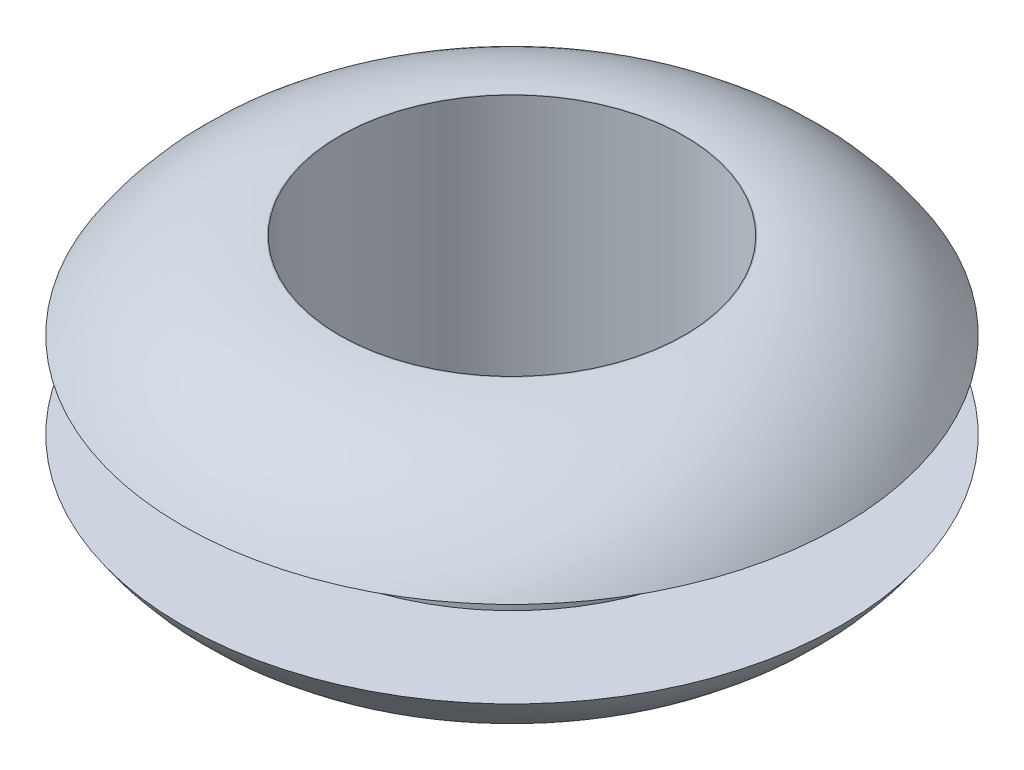
SolidWorks part; units mm, degrees
ref_plane "Front Plane" through (0, 0, 0) normal (0, 0, 1) x (1, 0, 0)
ref_plane "Top Plane" through (0, 0, 0) normal (0, 1, 0) x (1, 0, 0)
ref_plane "Right Plane" through (0, 0, 0) normal (1, 0, 0) x (0, 0, -1)
sketch "Sketch1" plane through (0, 0, 0) normal (0, 1, 0) x (1, 0, 0)
  circle A0 centre (0, 0) radius 7.65
  circle A1 centre (0, 0) radius 4
  dimension "D1" = 15.3
  dimension "D2" = 8
extrude "Boss-Extrude1" add sketch "Sketch1" along normal blind 6
ref_plane "Plane1" through (0, 3, 0) normal (0, 1, 0) x (1, 0, 0)
sketch "Sketch2" plane through (0, 3, 0) normal (0, 1, 0) x (1, 0, 0)
  circle A0 centre (0, 0) radius 7.65 construction
  circle A1 centre (0, 0) radius 7.65
  circle A2 centre (0, 0) radius 5
  dimension "D1" = 10
extrude "Cut-Extrude1" cut sketch "Sketch2" against normal mid plane 2
fillet "Fillet1" radius 4.3 2 edges at (0, 0, 7.65) (0, 6, 7.65)
